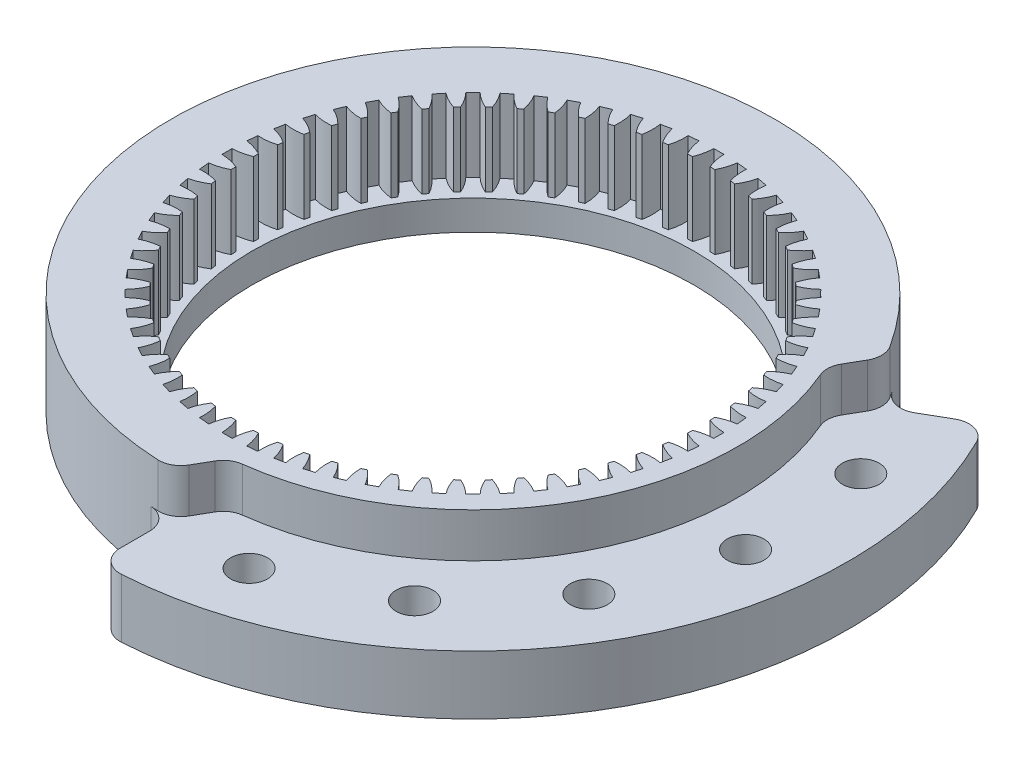
SolidWorks part; units mm, degrees
ref_plane "Front Plane" through (0, 0, 0) normal (0, 0, 1) x (1, 0, 0)
ref_plane "Top Plane" through (0, 0, 0) normal (0, 1, 0) x (1, 0, 0)
ref_plane "Right Plane" through (0, 0, 0) normal (1, 0, 0) x (0, 0, -1)
sketch "Sketch1" plane through (0, 0, 0) normal (0, 1, 0) x (1, 0, 0)
  circle A0 centre (0, 0) radius 16
  circle A1 centre (0, 0) radius 16.7
  circle A2 centre (0, 0) radius 15.5
  dimension "D1" = 32
  dimension "D2" = 33.4
  dimension "D3" = 1.2
extrude "Boss-Extrude1" add sketch "Sketch1" along normal mid plane 5 contours A1 A0 | A0 A2 | A2 region at (-15.5475, 0, 0) region at (-16.2277, 0, 0) region at (0, 0, 0)
sketch "Sketch7" plane through (0, 0, 0) normal (0, 1, 0) x (1, 0, 0)
  line L0 (16.7, 0) -> (-16.7, 0) construction
  line L1 (0, 16.7) -> (0, -16.7) construction
  circle A0 centre (0, 0) radius 16.7 construction
  point P7 (0, 0)
sketch "Sketch4" plane through (0, 0, 0) normal (0, 1, 0) x (1, 0, 0)
  line L0 (0, 0) -> (0, -25.5) construction
  line L10 (0, 0) -> (22.0836, 12.75) construction
  line L11 (22.0836, 12.75) -> (17.7535, 10.25)
  line L12 (0, -25.5) -> (0, -20.5)
  circle A2 centre (0, 0) radius 15.5 construction
  circle A3 centre (0, 0) radius 15.5
  arc A4 (17.7535, 10.25) -> (0, -20.5) centre (0, 0) ccw
  circle A9 centre (0, 0) radius 25.5 construction
  arc A10 (22.0836, 12.75) -> (0, -25.5) centre (0, 0) cw
  dimension "D1" = 5
  dimension "D3" = 120
  dimension "D2" = 5
extrude "Boss-Extrude2" add sketch "Sketch4" along normal mid plane 5
sketch "Sketch3" plane through (0, 0, 0) normal (0, 1, 0) x (1, 0, 0)
  line L0 (0, 0) -> (0, 16.7) construction
  line L1 (-0.3927, 15.9952) -> (0.3927, 15.9952) construction
  line L2 (-0.3434, 15.4962) -> (0, 0) construction
  line L3 (0, 13.7683) -> (-0.5155, 16.692) construction
  line L4 (0, 0) -> (0.8194, 16.6799) construction
  line L5 (0.3927, 15.9952) -> (1.177, 15.9566) construction
  line L6 (0, 15.5) -> (0, 16.7) construction
  line L7 (0.3434, 15.4962) -> (0.3434, 16.7) construction
  line L8 (0.3434, 16.0981) -> (-0.3121, 16.0981) construction
  arc A1 (-0.5957, 16.6894) -> (-0.3434, 15.4962) centre (-3.6364, 15.4232) cw construction
  arc A2 (0.5957, 16.6894) -> (0.3434, 15.4962) centre (3.6364, 15.4232) ccw construction
  circle A3 centre (0, 0) radius 15.5 construction
  arc A4 (0.3434, 15.4962) -> (-0.3434, 15.4962) centre (0, 0) ccw construction
  circle A5 centre (0, 0) radius 16 construction
  circle A6 centre (0, 0) radius 16.7 construction
  arc A7 (0.5957, 15.5068) -> (-0.5957, 15.5068) centre (0, 32.1962) cw
  arc A8 (0.5957, 16.6894) -> (-0.5957, 16.6894) centre (0, 0) ccw construction
  arc A9 (-0.5957, 15.5068) -> (-0.3434, 16.7) centre (-3.6364, 16.773) ccw
  arc A10 (0.5957, 15.5068) -> (0.3434, 16.7) centre (3.6364, 16.773) cw
  arc A11 (0.3434, 16.7) -> (-0.3434, 16.7) centre (0, 32.1962) cw
  dimension "D3" = 2.813
  dimension "D2" = 10
extrude "Cut-Extrude1" cut sketch "Sketch3" against normal through all both and the other way through all
pattern_circular "CirPattern1" count 64 over 360 about axis through (0, 2.5, 0) along (0, 1, 0) of "Cut-Extrude1"
sketch "Sketch5" plane through (0, 0, 0) normal (0, 1, 0) x (1, 0, 0)
  circle A0 centre (0, 0) radius 15.5183
extrude "Cut-Extrude2" cut sketch "Sketch5" against normal through all both and the other way through all
sketch "Sketch8" plane through (0, -2.5, 0) normal (0, -1, 0) x (1, 0, 0)
  line L2 (0, 25.5) -> (0, 20.5)
  line L6 (0, 25.5) -> (0, 20.5)
  line L8 (17.7535, -10.25) -> (22.0836, -12.75)
  line L9 (17.7535, -10.25) -> (22.0836, -12.75)
  circle A0 centre (0, 0) radius 15
  arc A3 (22.0836, -12.75) -> (0, 25.5) centre (0, 0) ccw
  arc A4 (22.0836, -12.75) -> (0, 25.5) centre (0, 0) ccw
  arc A5 (0, 20.5) -> (17.7535, -10.25) centre (0, 0) ccw
  arc A7 (0, 20.5) -> (17.7535, -10.25) centre (0, 0) ccw
  dimension "D2" = 30
  dimension "D1" = 0
extrude "Boss-Extrude3" add sketch "Sketch8" along normal blind 2
sketch "Sketch6" plane through (0, 2.5, 0) normal (0, 1, 0) x (1, 0, 0)
  line L0 (0, 0) -> (5.5646, -20.7674) construction
  line L2 (0, -16.7) -> (0, 16.7) construction
  circle A3 centre (5.5646, -20.7674) radius 0.5
  point P11 (0, 0)
  dimension "D2" = 15
  dimension "D1" = 1
  dimension "D3" = 21.5
extrude "Cut-Extrude3" cut sketch "Sketch6" against normal through all
pattern_circular "CirPattern2" count 5 every 22.5 about axis through (0, -2.5, 0) along (0, -1, 0) of "Cut-Extrude3" reverse direction yes
sketch "Sketch9" plane through (0, 2.5, 0) normal (0, 1, 0) x (1, 0, 0)
  line L0 (17.7535, 10.25) -> (16.275, 7.6892)
  line L1 (0, -20.5) -> (1.4785, -17.9392)
  line L2 (0, 0) -> (18.6195, -10.75) construction
  line L3 (1.4785, -17.9392) -> (16.275, 7.6892) construction
  line L4 (17.7535, 10.25) -> (22.0836, 12.75)
  line L5 (0, -20.5) -> (0, -25.5)
  arc A0 (1.4785, -17.9392) -> (16.275, 7.6892) centre (0, 0) ccw
  arc A1 (0, -25.5) -> (22.0836, 12.75) centre (0, 0) ccw construction
  arc A2 (0, -25.5) -> (22.0836, 12.75) centre (0, 0) ccw
  point P5 (8.8768, -5.125)
  dimension "D1" = 36
extrude "Cut-Extrude4" cut sketch "Sketch9" against normal offset from surface (3 mm away) 4 up to face at (13.2797, -4.5, 17.519)
fillet "Fillet1" radius 1.5 6 edges at (17.7535, -2.5, -10.25) (22.0836, -2.5, -12.75) (0, -2.5, 25.5) (0, -2.5, 20.5) (16.275, 1, -7.6892) (1.4785, 1, 17.9392)
fillet "Fillet2" radius 1.5 2 edges at (0, 1, 20.5) (17.7535, 1, -10.25)
sketch "Sketch12" plane through (0, -4.5, 0) normal (0, -1, 0) x (-1, 0, 0)
  point P0 (-5.5646, -20.7674)
  point P3 (-13.0884, -17.0571)
  point P6 (-18.6195, -10.75)
  point P9 (-21.3161, -2.8063)
  point P12 (-20.7674, 5.5646)
hole_wizard "Ø2.5mm Dowel Hole1" positions "Sketch12" profile "Sketch11" hole size "Ø2.5" standard "ISO"
sketch "Sketch11" plane through (5.5646, -4.5, 20.7674) normal (1, 0, 0) x (0, 0, -1)
  line L0 (0, 0) -> (0, 4.7511)
  line L1 (0, 4.7511) -> (1.25, 4)
  line L2 (1.25, 4) -> (1.25, 0)
  line L5 (1.25, 0) -> (0, 0)
  line L10 (0, 4.7511) -> (-1.25, 4) construction
  line L11 (0, -6.35) -> (0, 107.95) construction
  dimension "Hole Dia." = 2.5
  dimension "Hole Depth" = 4
  dimension "Drill Angle" = 118
ref_axis "Axis2" through (0, -4.5, 0) along (0, 1, 0)
equation "\"Module\"= .5"
equation "\"Number of Teeth\"=64"
equation "\"D1@Sketch1\"=\"Module\"* \"Number of Teeth\""
equation "\"D2@Sketch1\"=(\"Number of Teeth\" + 2) * \"Module\" + .4"
equation "\"D3@Sketch1\"=\"Module\" * if( \"Module\" => 1.25, 2.25, 2.4)"
equation "\"D3@Sketch3\"=180 / \"Number of Teeth\""
equation "\"D1@CirPattern1\"=\"Number of Teeth\""
